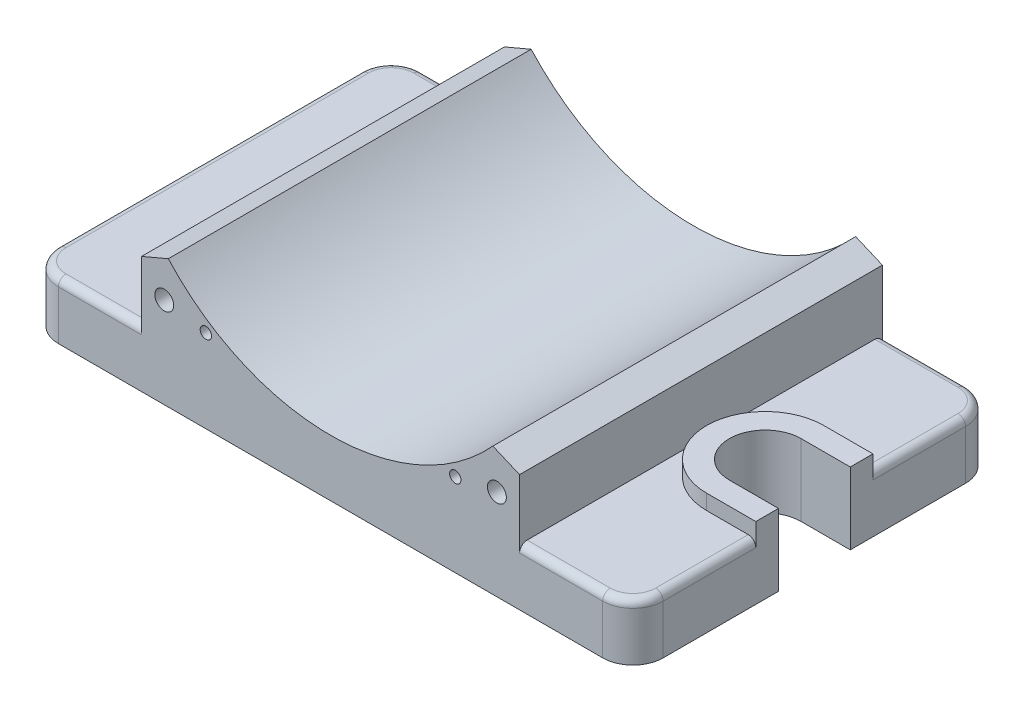
SolidWorks part; units mm, degrees
note: The reader was unsure of these and kept them because the rebuilt part matched: shared geometry of "草圖2<3>".
ref_plane "前基準面" through (0, 0, 0) normal (0, 0, 1) x (1, 0, 0)
ref_plane "上基準面" through (0, 0, 0) normal (0, 1, 0) x (1, 0, 0)
ref_plane "右基準面" through (0, 0, 0) normal (1, 0, 0) x (0, 0, -1)
sketch "草圖1" plane through (0, 0, 0) normal (0, 1, 0) x (1, 0, 0)
  line L0 (-80, 48) -> (80, -48) construction
  line L1 (-72, 48) -> (72, 48)
  line L2 (-80, 40) -> (-80, -40)
  line L3 (-72, -48) -> (72, -48)
  line L4 (80, 40) -> (80, -40)
  arc A0 (72, 48) -> (80, 40) centre (72, 40) cw
  arc A1 (-80, -40) -> (-72, -48) centre (-72, -40) ccw
  arc A2 (-72, 48) -> (-80, 40) centre (-72, 40) ccw
  arc A3 (72, -48) -> (80, -40) centre (72, -40) ccw
  point P9 (-80, -48)
  dimension "D3" = 8
  dimension "D1" = 96
  dimension "D2" = 160
extrude "伸長1" add sketch "草圖1" along normal blind 15
sketch "草圖3" plane through (0, 0, 0) normal (0, 0, 1) x (1, 0, 0)
  line L0 (0, 0) -> (0, 73) construction
  line L1 (-72, 0) -> (72, 0) construction
  line L2 (-72, 15) -> (72, 15) construction
  line L3 (50, 15) -> (50, 31)
  line L4 (50, 31) -> (42.9302, 34)
  line L5 (0, 15) -> (50, 15)
  arc A0 (42.9302, 34) -> (0, 15) centre (0, 73) cw
  dimension "D1" = 58
  dimension "D2" = 34
  dimension "D3" = 31
  dimension "D4" = 50
extrude "伸長2" add sketch "草圖3" along normal mid plane 96
mirror "鏡射1" about plane through (0, 0, 0) normal (1, 0, 0) of "伸長2"
hole_wizard "M6 螺紋孔1" positions "草圖5" profile "草圖4" tap size "M6" standard "ISO"
sketch "草圖5" plane through (0, 0, 48) normal (0, 0, 1) x (1, 0, 0)
  line L0 (0, 0) -> (0, 32.8569) construction
  line L1 (50, 15) -> (72, 15) construction
  point P0 (44, 24)
  point P3 (-44, 24)
  dimension "D1" = 88
  dimension "D2" = 9
sketch "草圖4" plane through (44, 24, 48) normal (1, 0, 0) x (0, -1, 0)
  line L0 (0, 0) -> (0, 20.5022)
  line L1 (0, 20.5022) -> (2.5, 19)
  line L2 (2.5, 19) -> (2.5, 0)
  line L5 (2.5, 0) -> (0, 0)
  line L10 (0, 20.5022) -> (-2.5, 19) construction
  line L11 (0, -6.35) -> (0, 107.95) construction
  dimension "螺孔鑽直徑" = 5
  dimension "螺孔鑽深度" = 19
  dimension "導頭角度" = 118
cosmetic thread "鑽孔螺紋1" parameters "D1"=16, "D2"=6
cosmetic thread "鑽孔螺紋2" parameters "D1"=16, "D2"=6
hole_wizard "Ø3.0 (3) 直徑孔1" positions "草圖7" profile "草圖6" hole size "Ø3.0" standard "ISO"
sketch "草圖7" plane through (0, 0, 48) normal (0, 0, 1) x (1, 0, 0)
  line L0 (0, 0) -> (0, 28.8305) construction
  line L1 (50, 15) -> (72, 15) construction
  point P0 (33, 22)
  point P5 (-33, 22)
  dimension "D1" = 66
  dimension "D2" = 7
sketch "草圖6" plane through (33, 22, 48) normal (1, 0, 0) x (0, -1, 0)
  line L0 (0, 0) -> (0, 9.9013)
  line L1 (0, 9.9013) -> (1.5, 9)
  line L2 (1.5, 9) -> (1.5, 0)
  line L5 (1.5, 0) -> (0, 0)
  line L10 (0, 9.9013) -> (-1.5, 9) construction
  line L11 (0, -6.35) -> (0, 107.95) construction
  dimension "鑽孔直徑" = 3
  dimension "鑽孔深度" = 9
  dimension "導頭角度" = 118
fillet "圓角1" radius 2 10 edges at (-61, 15, -48) (-77.6569, 15, -45.6569) (-80, 15, 0) (-77.6569, 15, 45.6569) (61, 15, -48) (77.6569, 15, -45.6569) (61, 15, 48) (77.6569, 15, 45.6569) (-61, 15, 48) (80, 15, 0)
sketch "草圖2" plane through (0, 0, 0) normal (0, 1, 0) x (1, 0, 0)
  line L0 (80, 9.5) -> (67, 9.5)
  line L1 (80, -40) -> (80, 40) construction
  line L2 (67, -9.5) -> (80, -9.5)
  line L3 (80, 15.5) -> (67, 15.5)
  line L4 (67, -15.5) -> (80, -15.5)
  line L5 (80, -15.5) -> (80, 15.5)
  arc A0 (67, 9.5) -> (67, -9.5) centre (67, 0) ccw
  arc A1 (67, 15.5) -> (67, -15.5) centre (67, 0) ccw
  line M26 (80, 40) -> (80, -40)
  dimension "D3" = 13
  dimension "D1" = 19
  dimension "D2" = 31
extrude "伸長3" add sketch "草圖2" along normal blind 19 contours A1 L3 L0 A0 L2 L4 M26
extrude "伸長4" cut sketch "草圖2<3>" along normal through all contours A0 L0 L2 M26
sketch "草圖2<3>" plane through (0, 0, 0) normal (0, 1, 0) x (1, 0, 0) same geometry as "草圖2"
